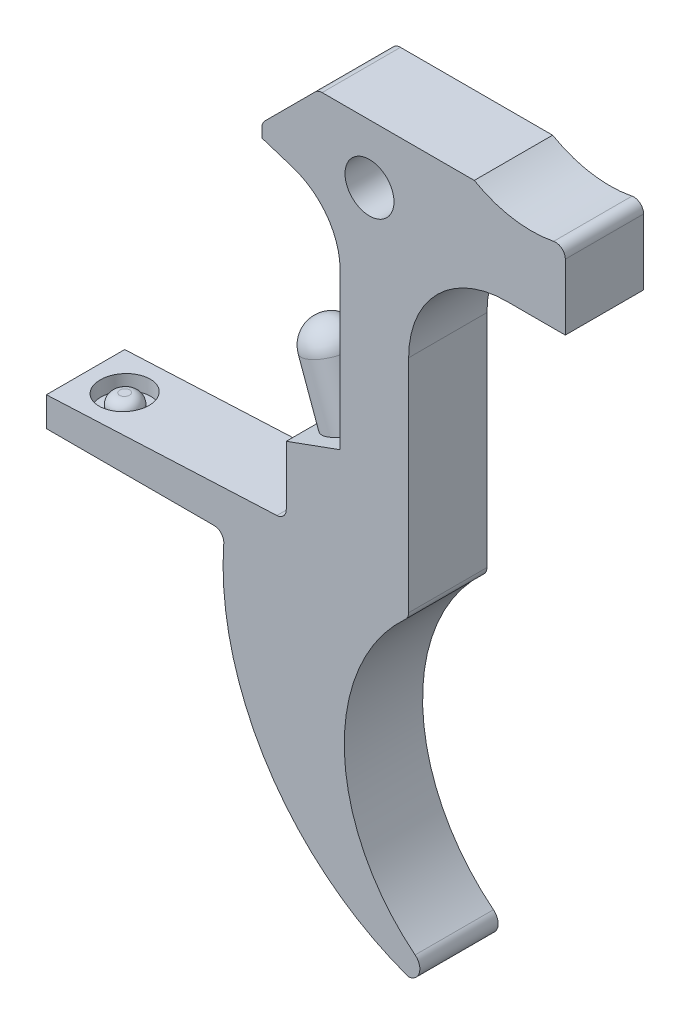
SolidWorks part; units mm, degrees
ref_plane "정면" through (0, 0, 0) normal (0, 0, 1) x (1, 0, 0)
ref_plane "윗면" through (0, 0, 0) normal (0, 1, 0) x (1, 0, 0)
ref_plane "우측면" through (0, 0, 0) normal (1, 0, 0) x (0, 0, -1)
sketch "스케치1" plane through (0, 0, 0) normal (0, 0, 1) x (1, 0, 0)
  line L0 (-8.5, -26.6754) -> (5.7296, -26.6754) construction
  line L1 (-10.9826, 0.2674) -> (-5.25, 6)
  line L2 (10.7038, 6) -> (-5.25, 6)
  line L3 (-10.9826, 0.2674) -> (-10.9826, -1.0988)
  line L5 (-3, -8.7708) -> (-3, -24.6736)
  line L6 (-3, -24.6736) -> (-8.5, -26.6754)
  line L7 (-8.5, -26.6754) -> (-8.5, -33.6754)
  line L9 (-33, -37.8094) -> (-33, -34.8094)
  line L10 (-33, -37.8094) -> (-14.7854, -37.8094)
  line L11 (-10.9826, -1.0988) -> (-7.8511, -2.1088)
  line L13 (-33, -34.8094) -> (-8.5, -33.6754)
  line L18 (4, -36.0388) -> (4, -13.0388)
  line L19 (14, -3.0388) -> (20, -3.0388)
  line L20 (20, -3.0388) -> (20, 4.9612)
  circle A0 centre (0, 0) radius 2.5
  arc A1 (4, -13.0388) -> (14, -3.0388) centre (14, -13.0388) cw
  arc A2 (4, -36.0388) -> (4.661, -65.5266) centre (16.6272, -50.5071) ccw
  arc A3 (4, -67.8094) -> (4.661, -65.5266) centre (3.8602, -66.5318) ccw
  arc A4 (20, 4.9612) -> (10.7038, 6) centre (16.5482, 16.1861) cw
  arc A5 (4, -67.8094) -> (-14.7854, -37.8094) centre (13.6308, -40.8973) cw
  arc A6 (-3, -8.7708) -> (-7.8511, -2.1088) centre (-10, -8.7708) ccw
  point P25 (4, -3.0388)
  point P30 (-3, -3.6736)
  point P32 (-10.9826, 6)
  dimension "D1" = 5
  dimension "D15" = 10
  dimension "D21" = 19.2035
  dimension "D22" = 3
  dimension "D5" = 7
  dimension "D2" = 20
  dimension "D3" = 33
  dimension "D4" = 31
  dimension "D6" = 8
  dimension "D7" = 6
  dimension "D8" = 21
  dimension "D9" = 5.5
  dimension "D10" = 7
  dimension "D11" = 9.3541
  dimension "D12" = 20
  dimension "D13" = 16
extrude "보스-돌출1" add sketch "스케치1" along normal blind 8 contours L0 L7 L10 A3 A2 L18 | L6 L0 L18 A1 L19 L20 L2 L3 L5 A0 region at (3.4275, -5.7282, 0) region at (-7.5586, -42.9245, 0)
sketch "스케치2" plane through (-3, 0, 0) normal (-1, 0, 0) x (0, 0, 1)
  line L0 (4, -3.6736) -> (4, -9.6736) construction
  circle A0 centre (4, -9.6736) radius 2.5
  dimension "D1" = 5
  dimension "D2" = 6
fillet "필렛8" radius 1 3 edges at (-8.5, -33.6754, 4) (-14.7854, -37.8094, 4) (4, -36.0388, 4)
extrude "보스-돌출2" add sketch "스케치2" along normal blind 2.5
fillet "필렛7" radius 2.5 1 edges at (-5.5, -12.1736, 4)
sketch "스케치3" plane through (7.579, -20.8231, 0) normal (-0.342, 0.9397, 0) x (0.9397, 0.342, 0)
  line L0 (-11.2579, 0) -> (-17.1109, -8) construction
  circle A0 centre (-14.1844, -4) radius 2.5
  dimension "D1" = 5
extrude "보스-돌출3" add sketch "스케치3" along normal blind 8.7
fillet "필렛4" radius 2.5 1 edges at (-11.0748, -18.3542, 4)
fillet "필렛5" radius 1 1 edges at (20, 4.9612, 4)
fillet "필렛6" radius 1 2 edges at (-5.25, 6, 4) (-10.9826, 0.2674, 4)
sketch "스케치4" plane through (0, -3.0388, 0) normal (0, -1, 0) x (1, 0, 0)
  circle A0 centre (16.726, 4) radius 2.5
  dimension "D1" = 5
extrude "컷-돌출1" cut sketch "스케치4" against normal blind 3
sketch "스케치5" plane through (1.5372, -33.2109, 0) normal (-0.0462, 0.9989, 0) x (0.9989, 0.0462, 0)
  line L0 (-34.5741, -8) -> (-34.5741, 0) construction
  circle A0 centre (-30.5741, -4) radius 2.5
  point P0 (-34.5741, -4)
  dimension "D1" = 5
  dimension "D2" = 4
extrude "컷-돌출2" cut sketch "스케치5" against normal blind 1.5
sketch "스케치7" plane through (1.6065, -34.7093, 0) normal (-0.0462, 0.9989, 0) x (0.9989, 0.0462, 0)
  circle A0 centre (-30.5741, -4) radius 1.5
extrude "보스-돌출4" add sketch "스케치7" along normal blind 1.5
fillet "필렛9" radius 1 1 edges at (-30.5027, -34.6938, 4)
